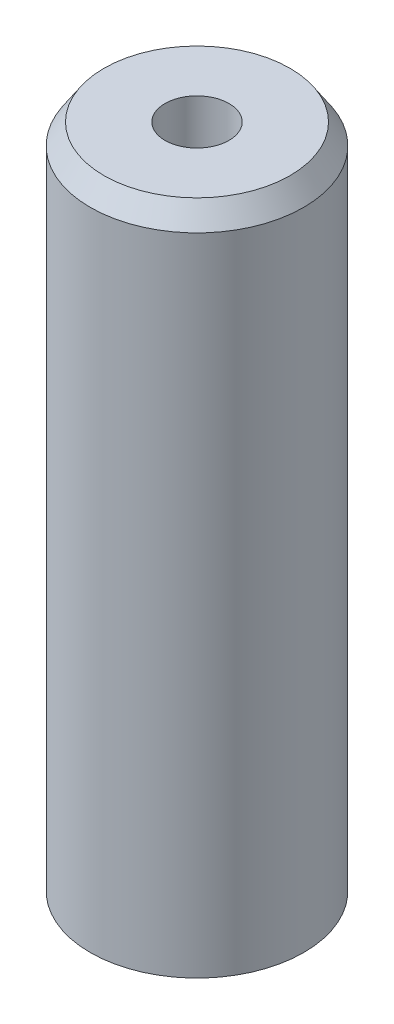
SolidWorks part; units mm, degrees
ref_plane "Front Plane" through (0, 0, 0) normal (0, 0, 1) x (1, 0, 0)
ref_plane "Top Plane" through (0, 0, 0) normal (0, 1, 0) x (1, 0, 0)
ref_plane "Right Plane" through (0, 0, 0) normal (1, 0, 0) x (0, 0, -1)
sketch "Sketch1" plane through (0, 0, 0) normal (0, 1, 0) x (1, 0, 0)
  circle A0 centre (0, 0) radius 27.5
  dimension "SHAFT_OD" = 55
extrude "Boss-Extrude1" add sketch "Sketch1" along normal blind 175.1814
sketch "Sketch2" plane through (0, 0, 0) normal (0, 1, 0) x (1, 0, 0)
  circle A0 centre (0, 0) radius 8.2481
  dimension "BORE_D" = 16.4962
extrude "Cut-Extrude1" cut sketch "Sketch2" along normal through all
chamfer "Chamfer1" distance 5.3249 angle 33.522 2 edges at (0, 175.1814, 27.5) (0, 0, 27.5) first distance on face at (0, 175.1814, 27.5) first distance on face at (0, 0, 8.2481)
